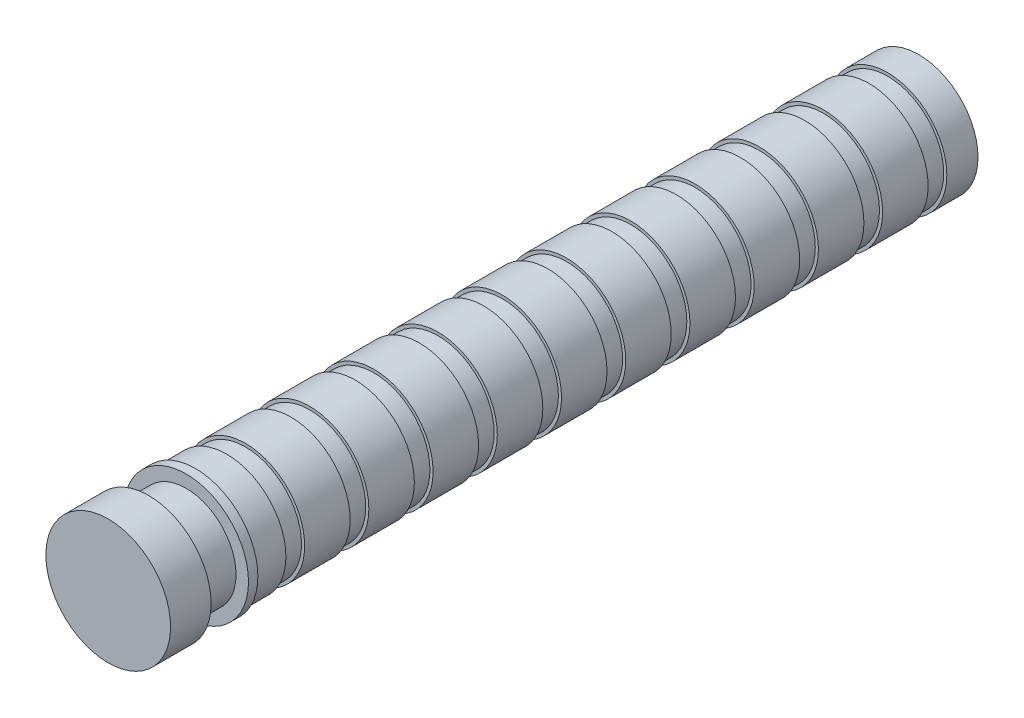
SolidWorks part; units mm, degrees
ref_plane "Front Plane" through (0, 0, 0) normal (0, 0, 1) x (1, 0, 0)
ref_plane "Top Plane" through (0, 0, 0) normal (0, 1, 0) x (1, 0, 0)
ref_plane "Right Plane" through (0, 0, 0) normal (1, 0, 0) x (0, 0, -1)
sketch "Sketch2" plane through (0, 0, 0) normal (1, 0, 0) x (0, 0, -1)
  line L0 (-29, 0) -> (29, 0)
  line L2 (-29, 4.75) -> (-26.5, 4.75)
  line L3 (29, 4.75) -> (29, 0)
  line L4 (-26.5, 4.75) -> (-26.5, 4.5)
  line L5 (-26.5, 4.5) -> (-25, 4.5)
  line L6 (-25, 4.5) -> (-25, 4.75)
  line L7 (-21.35, 4.75) -> (-21.35, 4.5)
  line L8 (-21.35, 4.5) -> (-19.85, 4.5)
  line L9 (-19.85, 4.5) -> (-19.85, 4.75)
  line L10 (-16.2, 4.75) -> (-16.2, 4.5)
  line L11 (-16.2, 4.5) -> (-14.7, 4.5)
  line L12 (-14.7, 4.5) -> (-14.7, 4.75)
  line L13 (-11.05, 4.75) -> (-11.05, 4.5)
  line L14 (-11.05, 4.5) -> (-9.55, 4.5)
  line L15 (-9.55, 4.5) -> (-9.55, 4.75)
  line L16 (-5.9, 4.75) -> (-5.9, 4.5)
  line L17 (-5.9, 4.5) -> (-4.4, 4.5)
  line L18 (-4.4, 4.5) -> (-4.4, 4.75)
  line L19 (-0.75, 4.75) -> (-0.75, 4.5)
  line L20 (-0.75, 4.5) -> (0.75, 4.5)
  line L21 (0.75, 4.5) -> (0.75, 4.75)
  line L22 (4.4, 4.75) -> (4.4, 4.5)
  line L23 (4.4, 4.5) -> (5.9, 4.5)
  line L24 (5.9, 4.5) -> (5.9, 4.75)
  line L25 (9.55, 4.75) -> (9.55, 4.5)
  line L26 (9.55, 4.5) -> (11.05, 4.5)
  line L27 (11.05, 4.5) -> (11.05, 4.75)
  line L28 (14.7, 4.75) -> (14.7, 4.5)
  line L29 (14.7, 4.5) -> (16.2, 4.5)
  line L30 (16.2, 4.5) -> (16.2, 4.75)
  line L31 (-25, 4.75) -> (-21.35, 4.75)
  line L32 (-19.85, 4.75) -> (-16.2, 4.75)
  line L33 (-14.7, 4.75) -> (-11.05, 4.75)
  line L34 (-9.55, 4.75) -> (-5.9, 4.75)
  line L35 (-4.4, 4.75) -> (-0.75, 4.75)
  line L36 (0.75, 4.75) -> (4.4, 4.75)
  line L37 (5.9, 4.75) -> (9.55, 4.75)
  line L38 (29, 0) -> (30.5762, 0) construction
  line L39 (11.05, 4.75) -> (14.7, 4.75)
  line L40 (16.2, 4.75) -> (19.85, 4.75)
  line L41 (19.85, 4.75) -> (19.85, 4.5)
  line L42 (19.85, 4.5) -> (21.35, 4.5)
  line L43 (21.35, 4.5) -> (21.35, 4.75)
  line L44 (25, 4.75) -> (25, 4.5)
  line L45 (25, 4.5) -> (26.5, 4.5)
  line L46 (26.5, 4.5) -> (26.5, 4.75)
  line L47 (21.35, 4.75) -> (25, 4.75)
  line L48 (26.5, 4.75) -> (29, 4.75)
  line L49 (-29, 4.75) -> (-29, 5)
  line L50 (-29, 5) -> (-29.75, 5)
  line L51 (-36, 5) -> (-36, 0)
  line L52 (55, 0) -> (-55, 0) construction
  line L53 (-36, 0) -> (-29, 0)
  line L54 (-29.75, 5) -> (-29.75, 4)
  line L55 (-29.75, 4) -> (-32.75, 4)
  line L56 (-32.75, 4) -> (-32.75, 5)
  line L57 (-32.75, 5) -> (-36, 5)
  point P4 (0, 0)
  dimension "D1" = 58
  dimension "D2" = 4.75
  dimension "D3" = 1.5
  dimension "D4" = 0.25
  dimension "D5" = 7
  dimension "D7" = 2.5
  dimension "D8" = 3.65
  dimension "D9" = 0.25
  dimension "D10" = 3
  dimension "D11" = 0.75
  dimension "D12" = 1
  dimension "D6" = 11
revolve "Revolve2" add sketch "Sketch2" angle 360 about L38
sketch "Sketch3" plane through (0, 0, -29) normal (0, 0, -1) x (-1, 0, 0)
  line L1 (1.75, 0.9682) -> (1.75, -0.9682)
  arc A0 (1.75, 0.9682) -> (1.75, -0.9682) centre (0, 0) ccw
  dimension "D1" = 4
  dimension "D2" = 1.75
extrude "Cut-Extrude1" cut sketch "Sketch3" against normal blind 14
